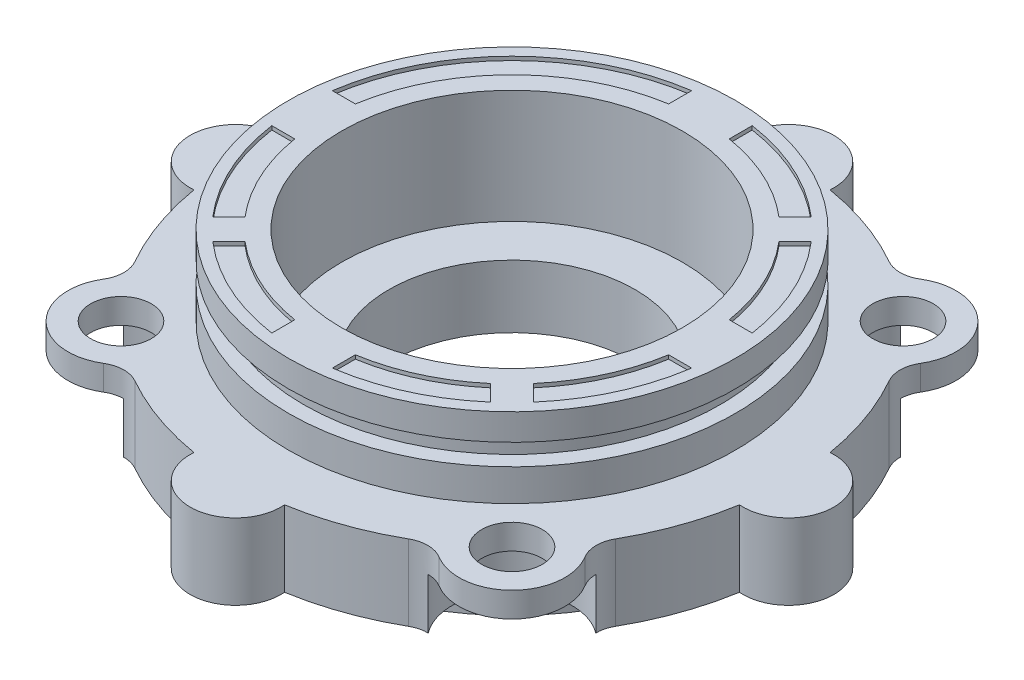
SolidWorks part; units mm, degrees
ref_plane "Front Plane" through (0, 0, 0) normal (0, 0, 1) x (1, 0, 0)
ref_plane "Top Plane" through (0, 0, 0) normal (0, 1, 0) x (1, 0, 0)
ref_plane "Right Plane" through (0, 0, 0) normal (1, 0, 0) x (0, 0, -1)
sketch "Sketch1" plane through (0, 0, 0) normal (0, 0, 1) x (1, 0, 0)
  line L0 (0, 0) -> (0, -50000) construction
  line L1 (16.25, -33.8076) -> (29.5, -33.8076)
  line L2 (29.5, -33.8076) -> (29.5, -31.0076)
  line L3 (29.5, -31.0076) -> (43.5, -31.0076)
  line L4 (43.5, -31.0076) -> (43.5, -21.0076)
  line L5 (43.5, -21.0076) -> (29.5, -21.0076)
  line L6 (29.5, -21.0076) -> (29.5, -16.8008)
  line L7 (29.5, -16.8008) -> (27.5, -16.8008)
  line L8 (27.5, -16.8008) -> (27.5, -14.0008)
  line L9 (27.5, -14.0008) -> (29.5, -14.0008)
  line L10 (29.5, -14.0008) -> (29.5, -10.5076)
  line L11 (29.5, -10.5076) -> (22.5, -10.5076)
  line L12 (16.25, -33.8076) -> (16.25, -25.5076)
  line L13 (16.25, -25.5076) -> (22.5, -25.5076)
  line L14 (22.5, -25.5076) -> (22.5, -10.5076)
  dimension "D1" = 2.8
  dimension "D2" = 43.5
  dimension "D3" = 10
  dimension "D4" = 29.5
  dimension "D5" = 23.3
  dimension "D6" = 2
  dimension "D7" = 29.5
  dimension "D8" = 2.8
  dimension "D9" = 22.5
  dimension "D10" = 16.25
  dimension "D11" = 15
revolve "Revolve1" add sketch "Sketch1" angle 360 about L0
sketch "Sketch2" plane through (0, -31.0076, 0) normal (0, -1, 0) x (1, 0, 0)
  line L0 (0, 0) -> (-25.8094, 25.8094)
  arc A0 (-5.9797, 36.0068) -> (-18.0755, 31.71) centre (0, 0) ccw
  arc A1 (36.0068, -5.9797) -> (36.0068, 5.9797) centre (36.5, 0) ccw
  arc A2 (-36.0068, -5.9797) -> (-31.71, -18.0755) centre (0, 0) ccw
  arc A4 (-5.9797, 36.0068) -> (-20.4078, 30.2617) centre (0, 0) ccw
  arc A5 (-5.9797, -36.0068) -> (5.9797, -36.0068) centre (0, -36.5) ccw
  arc A6 (-25.8094, 25.8094) -> (-31.71, -18.0755) centre (0, 0) ccw
  arc A8 (-25.8094, 25.8094) -> (-29.689, -21.2324) centre (0, 0) ccw
  arc A9 (-36.0068, 5.9797) -> (-36.0068, -5.9797) centre (-36.5, 0) ccw
  arc A10 (-25.8094, 25.8094) -> (-20.4078, -30.2617) centre (0, 0) ccw
  arc A12 (-25.8094, 25.8094) -> (-20.4078, -30.2617) centre (0, 0) ccw
  arc A13 (5.9797, 36.0068) -> (-5.9797, 36.0068) centre (0, 36.5) ccw
  arc A16 (18.0755, 31.71) -> (5.9797, 36.0068) centre (0, 0) ccw
  arc A17 (36.0068, 5.9797) -> (31.71, 18.0755) centre (0, 0) ccw
  arc A18 (29.689, -21.2324) -> (30.2617, -20.4078) centre (0, 0) ccw
  arc A19 (5.9797, -36.0068) -> (21.2324, -29.689) centre (0, 0) ccw
  arc A20 (-21.2324, -29.689) -> (-5.9797, -36.0068) centre (0, 0) ccw
  arc A21 (-36.0068, -5.9797) -> (-29.689, -21.2324) centre (0, 0) ccw
  arc A22 (-5.9797, 36.0068) -> (-36.0068, 5.9797) centre (0, 0) ccw
  arc A23 (29.689, 21.2324) -> (21.2324, 29.689) centre (25.8094, 25.8094) ccw [skipped]
  arc A24 (21.2324, -29.689) -> (29.689, -21.2324) centre (25.8094, -25.8094) ccw [skipped]
  arc A25 (-21.2324, 29.689) -> (-29.689, 21.2324) centre (-25.8094, 25.8094) ccw [skipped]
  arc A26 (-29.689, -21.2324) -> (-21.2324, -29.689) centre (-25.8094, -25.8094) ccw [skipped]
  arc A27 (-22.1484, 31.7757) -> (-31.7757, 22.1484) centre (-25.8094, 25.8094) ccw
  arc A28 (31.7757, 22.1484) -> (22.1484, 31.7757) centre (25.8094, 25.8094) ccw
  arc A29 (22.1484, -31.7757) -> (31.7757, -22.1484) centre (25.8094, -25.8094) ccw
  arc A30 (-31.7757, -22.1484) -> (-22.1484, -31.7757) centre (-25.8094, -25.8094) ccw
  circle A31 centre (0, 0) radius 36.5
  arc A32 (-31.71, 18.0755) -> (-36.0068, 5.9797) centre (0, 0) ccw
  arc A33 (21.2324, 29.689) -> (5.9797, 36.0068) centre (0, 0) ccw
  arc A34 (36.0068, 5.9797) -> (29.689, 21.2324) centre (0, 0) ccw
  arc A35 (29.689, -21.2324) -> (36.0068, -5.9797) centre (0, 0) ccw
  arc A36 (5.9797, -36.0068) -> (21.2324, -29.689) centre (0, 0) ccw
  arc A37 (-21.2324, -29.689) -> (-5.9797, -36.0068) centre (0, 0) ccw
  arc A38 (-36.0068, -5.9797) -> (5.9797, 36.0068) centre (0, 0) ccw
  arc A39 (-30.2617, 20.4078) -> (-36.0068, 5.9797) centre (0, 0) ccw
  arc A40 (-31.7757, 22.1484) -> (-31.71, 18.0755) centre (-35.1851, 20.0564) cw
  arc A41 (-22.1484, 31.7757) -> (-18.0755, 31.71) centre (-20.0564, 35.1851) ccw
  arc A42 (31.7757, 22.1484) -> (31.71, 18.0755) centre (35.1851, 20.0564) ccw
  arc A43 (22.1484, 31.7757) -> (18.0755, 31.71) centre (20.0564, 35.1851) cw
  arc A44 (22.1484, -31.7757) -> (18.0755, -31.71) centre (20.0564, -35.1851) ccw
  arc A45 (31.7757, -22.1484) -> (31.71, -18.0755) centre (35.1851, -20.0564) cw
  arc A46 (-31.7757, -22.1484) -> (-31.71, -18.0755) centre (-35.1851, -20.0564) ccw
  arc A47 (-22.1484, -31.7757) -> (-18.0755, -31.71) centre (-20.0564, -35.1851) cw
  arc A48 (18.0755, 31.71) -> (-20.4078, 30.2617) centre (0, 0) ccw
  arc A49 (18.0755, 31.71) -> (-20.4078, 30.2617) centre (0, 0) ccw
  arc A50 (18.0755, 31.71) -> (-20.4078, 30.2617) centre (0, 0) ccw
  arc A51 (18.0755, 31.71) -> (-20.4078, 30.2617) centre (0, 0) ccw
  arc A52 (-29.689, -21.2324) -> (21.2324, 29.689) centre (0, 0) ccw
  arc A53 (-21.2324, -29.689) -> (21.2324, 29.689) centre (0, 0) ccw
  arc A54 (-18.0755, -31.71) -> (21.2324, 29.689) centre (0, 0) ccw
  arc A55 (-18.0755, -31.71) -> (21.2324, 29.689) centre (0, 0) ccw
  arc A56 (31.71, -18.0755) -> (18.0755, -31.71) centre (0, 0) ccw
  arc A57 (31.71, -18.0755) -> (36.0068, -5.9797) centre (0, 0) ccw
  arc A58 (29.689, -21.2324) -> (30.2617, -20.4078) centre (0, 0) ccw [skipped]
  point P28 (0, 0)
  point P54 (0, 0)
  point P75 (0, 0)
  circle M17 centre (0, 0) radius 43.5
  dimension "D1" = 73
  dimension "D3" = 14
  dimension "D4" = 4
  dimension "D2" = 8
extrude "Cut-Extrude2" cut sketch "Sketch2" against normal through all contours A28 A27 A0 A13 A16 M17 | A29 A28 A2 A1 A18 M17 | A30 A29 A2 A5 A20 M17 | A30 A2 A9 A22 A27 M17 region at (-12.4283, -31.0076, 34.9863) region at (-33.385, -31.0076, 26.7038) region at (39.6083, -31.0076, 16.4063) region at (-26.7038, -31.0076, -33.385)
sketch "Sketch4" plane through (0, -31.0076, 0) normal (0, -1, 0) x (1, 0, 0)
  circle A2 centre (25.8094, 25.8094) radius 4
  circle A4 centre (0, 0) radius 29.5
  arc A5 (20.121, 31.1856) -> (31.1856, 20.121) centre (26.4489, 26.4489) ccw
  arc A6 (18.0755, 31.71) -> (22.1484, 31.7757) centre (20.0564, 35.1851) ccw construction
  arc A7 (31.7757, 22.1484) -> (31.71, 18.0755) centre (35.1851, 20.0564) ccw construction
  arc M14 (31.71, 18.0755) -> (31.7757, 22.1484) centre (35.1851, 20.0564) cw
  arc M15 (31.7757, 22.1484) -> (22.1484, 31.7757) centre (25.8094, 25.8094) ccw
  arc M16 (22.1484, 31.7757) -> (18.0755, 31.71) centre (20.0564, 35.1851) cw
  dimension "D1" = 8
extrude "Cut-Extrude3" cut sketch "Sketch4" against normal blind 6.7 contours A5 A2 M16 M14 M15 region at (18.7659, -31.0076, 25.8993)
sketch "Sketch5" plane through (0, -31.0076, 0) normal (0, -1, 0) x (1, 0, 0)
  circle A0 centre (25.8094, 25.8094) radius 4 construction
  circle A1 centre (25.8094, 25.8094) radius 4
extrude "Cut-Extrude4" cut sketch "Sketch5" against normal blind 36.7
pattern_circular "CirPattern1" count 4 over 360 about axis through (0, -31.0076, 0) along (0, -1, 0) of "Cut-Extrude3", "Cut-Extrude4"
sketch "Sketch6" plane through (0, -10.5076, 0) normal (0, 1, 0) x (1, 0, 0)
  line L0 (19.0352, 16.2068) -> (21.2132, 18.3848)
  line L1 (19.0919, -16.2635) -> (19.0352, -16.2068)
  line L2 (4, 27.7128) -> (4, 24.6779)
  line L3 (-4, 27.7128) -> (-4, 24.6779)
  line L4 (-27.7128, -4) -> (-24.6779, -4)
  line L5 (-27.7128, 4) -> (-24.6779, 4)
  line L6 (16.2635, -19.0919) -> (16.2068, -19.0352)
  line L7 (-16.2068, 19.0352) -> (-18.3848, 21.2132)
  line L8 (16.2068, 19.0352) -> (18.3848, 21.2132)
  line L9 (-4, -24.6779) -> (-4, -28)
  line L10 (16.2068, -19.0352) -> (18.3848, -21.2132)
  line L11 (-19.0352, 16.2068) -> (-21.2132, 18.3848)
  line L12 (19.0352, -16.2068) -> (21.2132, -18.3848)
  line L13 (-19.0352, -16.2068) -> (-21.2132, -18.3848)
  line L14 (24.6779, 4) -> (27.7128, 4)
  line L15 (-16.2068, -19.0352) -> (-18.3848, -21.2132)
  line L16 (24.6779, -4) -> (27.7128, -4)
  line L21 (4, -24.6779) -> (4, -28)
  arc A0 (-27.7128, -4) -> (-4, -27.7128) centre (0, 0) ccw
  arc A1 (-24.6779, -4) -> (-4, -24.6779) centre (0, 0) ccw
  arc A2 (4, -24.6779) -> (24.6779, -4) centre (0, 0) ccw
  arc A3 (4, -27.7128) -> (27.7128, -4) centre (0, 0) ccw
  arc A4 (24.6779, 4) -> (4, 24.6779) centre (0, 0) ccw
  arc A5 (27.7128, 4) -> (4, 27.7128) centre (0, 0) ccw
  arc A6 (-4, 27.7128) -> (-27.7128, 4) centre (0, 0) ccw
  arc A7 (-4, 24.6779) -> (-24.6779, 4) centre (0, 0) ccw
  point P8 (0, 0)
  point P11 (0, 0)
  point P46 (0, 0)
  circle M5 centre (0, 0) radius 22.5
  dimension "D1" = 56
  dimension "D2" = 50
extrude "Cut-Extrude5" cut sketch "Sketch6" against normal blind 0.5 contours A7 L3 A6 L7 | L8 A5 L2 A4 | L14 A5 L0 A4 | L12 A3 L16 A2 L1 | L21 A3 L10 L6 A2 | A1 L15 A0 L9 | A1 L4 A0 L13 | M5 | A6 L5 A7 L3 region at (23.8044, -10.5076, -10.9354) region at (10.9354, -10.5076, -23.8044) region at (23.8044, -10.5076, 10.9354) region at (10.9354, -10.5076, 23.8044) region at (-10.9354, -10.5076, -23.8044) region at (-23.8044, -10.5076, 10.9354) region at (-10.9354, -10.5076, 23.8044) region at (0, -10.5076, 0)
